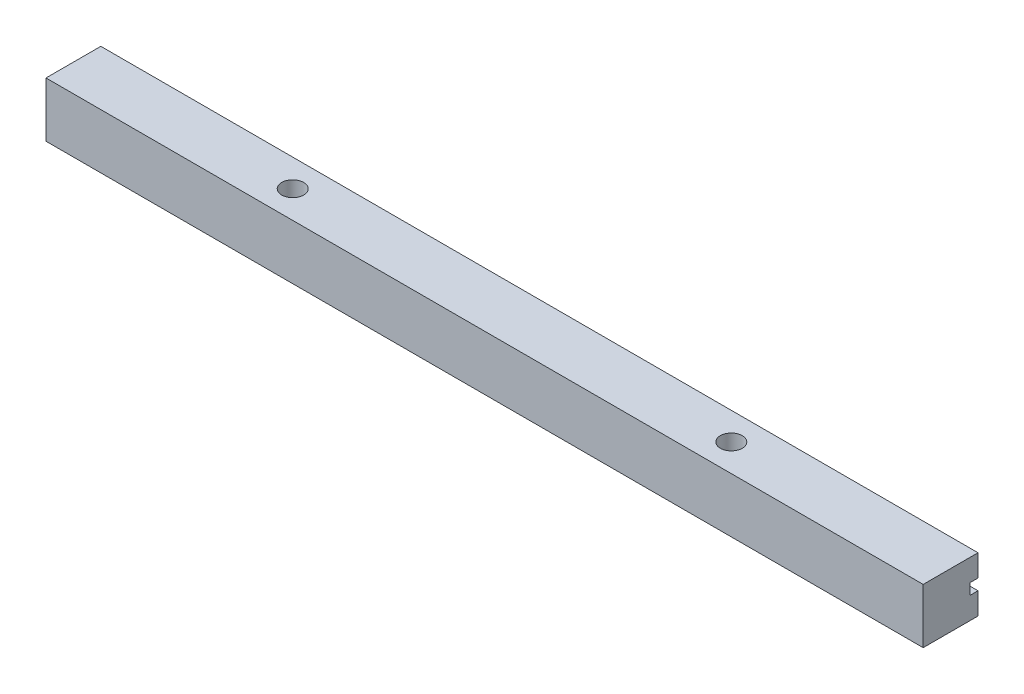
SolidWorks part; units mm, degrees
ref_plane "Ön Düzlem" through (0, 0, 0) normal (0, 0, 1) x (1, 0, 0)
ref_plane "Üst Düzlem" through (0, 0, 0) normal (0, 1, 0) x (1, 0, 0)
ref_plane "Sağ Düzlem" through (0, 0, 0) normal (1, 0, 0) x (0, 0, -1)
sketch "Sketch1" plane through (0, 0, 0) normal (0, 0, 1) x (1, 0, 0)
  line L1 (0, 0) -> (160, 0)
  line L2 (0, 0) -> (0, 10)
  line L3 (0, 10) -> (160, 10)
  line L4 (160, 0) -> (160, 10)
extrude "Boss-Extrude1" add sketch "Sketch1" along normal blind 10
sketch "Sketch2" plane through (0, 0, 0) normal (0, -1, 0) x (1, 0, 0)
  line L0 (0, 10) -> (0, 0) construction
  line L1 (160, 10) -> (160, 0) construction
  line L2 (0, 10) -> (160, 10) construction
  circle A0 centre (40, 5) radius 2
  circle A1 centre (120, 5) radius 2
  dimension "D1" = 40
  dimension "D2" = 40
  dimension "D3" = 5
  dimension "D4" = 5
extrude "Cut-Extrude1" cut sketch "Sketch2" against normal through all
sketch "Sketch5" plane through (0, 0, 0) normal (-1, 0, 0) x (0, 0, 1)
  line L0 (0, 10) -> (0, 0) construction
  line L1 (1.5, 6) -> (0, 6)
  line L2 (1.5, 6) -> (1.5, 4)
  line L3 (1.5, 4) -> (0, 4)
  line L4 (0, 6) -> (0, 4)
  line L5 (10, 10) -> (0, 10) construction
  dimension "D1" = 4
  dimension "D2" = 2
  dimension "D3" = 1.5
extrude "Cut-Extrude4" cut sketch "Sketch5" against normal through all
